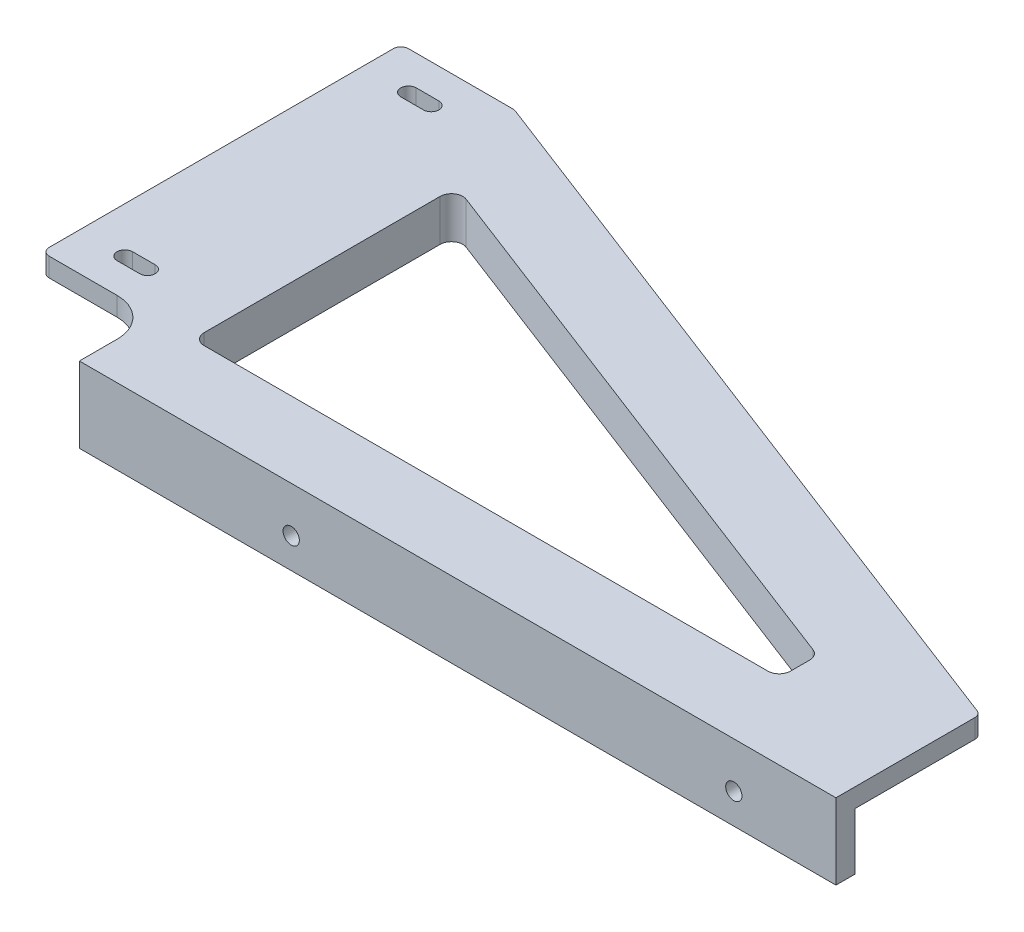
SolidWorks part; units mm, degrees
ref_plane "Front" through (0, 0, 0) normal (0, 0, 1) x (1, 0, 0)
ref_plane "Top" through (0, 0, 0) normal (0, 1, 0) x (1, 0, 0)
ref_plane "Right" through (0, 0, 0) normal (1, 0, 0) x (0, 0, -1)
other "Configuration Table"
sketch "Sketch1" plane through (0, 0, 0) normal (0, 1, 0) x (1, 0, 0)
  line L0 (-100, 0) -> (100, 0)
  line L1 (100, 0) -> (100, 38.1)
  line L3 (-130, 115) -> (-130, 20)
  line L4 (-100, 0) -> (-100, 10)
  line L5 (-110, 20) -> (-130, 20)
  line L6 (-130, 115) -> (-100, 115)
  line L7 (100, 38.1) -> (-100, 115)
  arc A0 (-100, 10) -> (-110, 20) centre (-110, 10) ccw
  point P0 (0, 0)
  dimension "D6" = 10
  dimension "D1" = 115
  dimension "D2" = 230
  dimension "D3" = 38.1
  dimension "D4" = 30
  dimension "D5" = 20
extrude "Boss-Extrude1" add sketch "Sketch1" along normal blind 5 contours L3 L5 A0 L4 L0 L1 L7 L6
sketch "Sketch2" plane through (0, 0, 0) normal (0, -1, 0) x (1, 0, 0)
  line L0 (-100, -5) -> (100, -5)
  line L2 (100, 0) -> (100, -38.1) construction
  line L3 (100, -5) -> (100, 0)
  line L4 (100, 0) -> (-100, 0)
  line L5 (-100, 0) -> (-100, -5)
  line L8 (-100, 0) -> (-100, -10) construction
  dimension "D1" = 5
extrude "Boss-Extrude2" add sketch "Sketch2" along normal blind 15 contours L4 L5 L0 L3
sketch "Sketch5" plane through (0, 0, 0) normal (0, -1, 0) x (1, 0, 0)
  line L1 (-53.5, -5) -> (-34.5, -5)
  line L3 (-48.5, -10) -> (-39.5, -10)
  line L5 (-53.5, -5) -> (-39.5, -10) construction
  line L6 (-34.5, -5) -> (-48.5, -10) construction
  line L7 (-100, -5) -> (100, -5) construction
  line L10 (68.5, -10) -> (77.5, -10)
  line L12 (73, 36.5599) -> (73, -36.1824) construction
  line L13 (77.5, -10) -> (82.5, -5)
  line L15 (-39.5, -10) -> (-34.5, -5)
  line L17 (-44, -13.3089) -> (-44, -5.4456) construction
  line L18 (-48.5, -10) -> (-53.5, -5)
  line L20 (-100, -5) -> (100, -5) construction
  line L21 (68.5, -10) -> (63.5, -5)
  line L22 (63.5, -5) -> (82.5, -5)
  line L23 (-100, 0) -> (-100, -5) construction
  point P4 (-44, -8.3929)
  point P5 (73, -10)
  point P11 (73, -10.0372)
  dimension "D1" = 9
  dimension "D2" = 5
  dimension "D3" = 9
  dimension "D4" = 5
  dimension "D5" = 56
  dimension "D6" = 173
  dimension "D7" = 225
  dimension "D8" = 135
extrude "Boss-Extrude3" add sketch "Sketch5" along normal up to surface (15 mm away) up to face at (0, -15, -2.5)
sketch "Sketch6" plane through (0, 0, 0) normal (0, 0, 1) x (1, 0, 0)
  line L2 (-100, 5) -> (100, 5) construction
  line L3 (-100, -15) -> (-100, 0) construction
  circle A0 centre (-44, -7) radius 2.15
  circle A1 centre (73, -7) radius 2.15
  point P8 (0, 0)
  dimension "D1" = 4.3
  dimension "D2" = 4.3
  dimension "D3" = 56
  dimension "D4" = 173
  dimension "D5" = 12
extrude "Cut-Extrude2" cut sketch "Sketch6" against normal through all
sketch "Sketch7" plane through (0, 0, -10) normal (0, 0, -1) x (-1, 0, 0)
  line L1 (-73, -11.0992) -> (-69.45, -9.0496)
  line L2 (-69.45, -9.0496) -> (-69.45, -4.9504)
  line L3 (-69.45, -4.9504) -> (-73, -2.9008)
  line L4 (-73, -2.9008) -> (-76.55, -4.9504)
  line L5 (-76.55, -4.9504) -> (-76.55, -9.0496)
  line L6 (-76.55, -9.0496) -> (-73, -11.0992)
  line L7 (47.55, -9.0496) -> (47.55, -4.9504)
  line L8 (47.55, -4.9504) -> (44, -2.9008)
  line L9 (44, -2.9008) -> (40.45, -4.9504)
  line L10 (40.45, -4.9504) -> (40.45, -9.0496)
  line L11 (40.45, -9.0496) -> (44, -11.0992)
  line L12 (44, -11.0992) -> (47.55, -9.0496)
  circle A0 centre (-73, -7) radius 3.55 construction
  circle A1 centre (44, -7) radius 3.55 construction
  point P1 (59, -7)
  dimension "D1" = 7.1
  dimension "D2" = 7.1
extrude "Cut-Extrude3" cut sketch "Sketch7" against normal blind 3.2
sketch "Sketch9" plane through (0, 0, 0) normal (0, -1, 0) x (1, 0, 0)
  line L0 (-130, -115) -> (-130, -20) construction
  line L1 (-125, -35.5) -> (-105, -35.5)
  line L2 (-125, -35.5) -> (-125, -24.5)
  line L3 (-125, -24.5) -> (-105, -24.5)
  line L4 (-105, -35.5) -> (-105, -24.5)
  line L5 (-125, -35.5) -> (-105, -24.5) construction
  line L6 (-125, -24.5) -> (-105, -35.5) construction
  line L7 (-125, -110.5) -> (-105, -110.5)
  line L8 (-125, -110.5) -> (-125, -99.5)
  line L9 (-125, -99.5) -> (-105, -99.5)
  line L10 (-105, -110.5) -> (-105, -99.5)
  line L11 (-125, -110.5) -> (-105, -99.5) construction
  line L12 (-125, -99.5) -> (-105, -110.5) construction
  line L13 (-130, -67.5) -> (-65.95, -67.5) construction
  point P0 (-115, -30)
  point P5 (-115, -105)
  point P10 (0, 0)
  point P15 (0, 0)
  point P16 (0, 0)
  point P17 (0, 0)
  dimension "D1" = 20
  dimension "D2" = 11
  dimension "D3" = 75
  dimension "D4" = 15
extrude "Boss-Extrude4" add sketch "Sketch9" along normal blind 2
chamfer "Chamfer1" distance 2 angle 45 8 edges at (-105, 0, -30) (-115, 0, -35.5) (-115, 0, -24.5) (-125, 0, -30) (-115, 0, -99.5) (-125, 0, -105) (-105, 0, -105) (-115, 0, -110.5)
sketch "Sketch8" plane through (0, -2, 0) normal (0, -1, 0) x (1, 0, 0)
  line L0 (-115, 7.2671) -> (-115, -126.9464) construction
  line L1 (-130, -115) -> (-130, -20) construction
  line L2 (-118, -30) -> (-112, -30) construction
  line L3 (-118, -27.95) -> (-112, -27.95)
  line L4 (-118, -32.05) -> (-112, -32.05)
  line L5 (-118, -105) -> (-112, -105) construction
  line L6 (-118, -102.95) -> (-112, -102.95)
  line L7 (-118, -107.05) -> (-112, -107.05)
  line L8 (-130, -67.5) -> (-41.0791, -67.5) construction
  arc A0 (-118, -27.95) -> (-118, -32.05) centre (-118, -30) ccw
  arc A1 (-112, -32.05) -> (-112, -27.95) centre (-112, -30) ccw
  arc A2 (-118, -102.95) -> (-118, -107.05) centre (-118, -105) ccw
  arc A3 (-112, -107.05) -> (-112, -102.95) centre (-112, -105) ccw
  point P6 (-115, -30)
  point P11 (-115, -105)
  point P18 (0, 0)
  dimension "D1" = 15
  dimension "D2" = 4.1
  dimension "D3" = 6
  dimension "D4" = 4.1
  dimension "D5" = 6
  dimension "D6" = 75
extrude "Cut-Extrude4" cut sketch "Sketch8" against normal through all
sketch "Sketch10" plane through (0, 0, 0) normal (0, -1, 0) x (1, 0, 0)
  line L0 (-90, -31.3983) -> (-90, -85.3599)
  line L1 (-85.9233, -88.1601) -> (63.0767, -30.8696)
  line L2 (65, -28.0694) -> (65, -23)
  line L3 (62, -20) -> (-87, -20)
  line L4 (-90, -23) -> (-90, -31.3983)
  line L5 (-130, -115) -> (-130, -20) construction
  line L7 (100, -38.1) -> (-100, -115) construction
  line L8 (-34.5, -5) -> (63.5, -5) construction
  line L9 (100, -5) -> (100, -38.1) construction
  arc A0 (-90, -85.3599) -> (-85.9233, -88.1601) centre (-87, -85.3599) ccw
  arc A1 (63.0767, -30.8696) -> (65, -28.0694) centre (62, -28.0694) ccw
  arc A2 (65, -23) -> (62, -20) centre (62, -23) ccw
  arc A3 (-87, -20) -> (-90, -23) centre (-87, -23) ccw
  dimension "D5" = 3
  dimension "D1" = 40
  dimension "D2" = 20
  dimension "D3" = 15
  dimension "D4" = 35
extrude "Cut-Extrude5" cut sketch "Sketch10" against normal through all contours L3 A3 L4 L0 A0 L1 A1 L2 A2
sketch "Sketch11" plane through (0, 0, 0) normal (0, -1, 0) x (1, 0, 0)
  line L6 (-90, -23) -> (-90, -85.3599) construction
  line L7 (-85.9233, -88.1601) -> (63.0767, -30.8696) construction
  line L8 (65, -28.0694) -> (65, -23) construction
  line L13 (62, -20) -> (-87, -20) construction
  line L14 (-90, -23) -> (-90, -85.3599)
  line L15 (-85.9233, -88.1601) -> (63.0767, -30.8696)
  line L16 (65, -28.0694) -> (65, -23)
  line L17 (62, -20) -> (-87, -20)
  line L18 (62, -17.75) -> (-87, -17.75)
  line L19 (-92.25, -23) -> (-92.25, -85.3599)
  line L20 (-85.1159, -90.2602) -> (63.8841, -32.9697)
  line L21 (67.25, -28.0694) -> (67.25, -23)
  arc A0 (-87, -20) -> (-90, -23) centre (-87, -23) ccw construction
  arc A1 (-90, -85.3599) -> (-85.9233, -88.1601) centre (-87, -85.3599) ccw construction
  arc A2 (63.0767, -30.8696) -> (65, -28.0694) centre (62, -28.0694) ccw construction
  arc A3 (65, -23) -> (62, -20) centre (62, -23) ccw construction
  arc A12 (-87, -20) -> (-90, -23) centre (-87, -23) ccw
  arc A13 (-90, -85.3599) -> (-85.9233, -88.1601) centre (-87, -85.3599) ccw
  arc A14 (63.0767, -30.8696) -> (65, -28.0694) centre (62, -28.0694) ccw
  arc A15 (65, -23) -> (62, -20) centre (62, -23) ccw
  arc A16 (-87, -17.75) -> (-92.25, -23) centre (-87, -23) ccw
  arc A17 (-92.25, -85.3599) -> (-85.1159, -90.2602) centre (-87, -85.3599) ccw
  arc A18 (63.8841, -32.9697) -> (67.25, -28.0694) centre (62, -28.0694) ccw
  arc A19 (67.25, -23) -> (62, -17.75) centre (62, -23) ccw
  dimension "D1" = 2.25
extrude "Boss-Extrude5" add sketch "Sketch11" along normal blind 6
fillet "Fillet1" radius 2 4 edges at (-130, 2.5, -20) (-130, 2.5, -115) (-100, 2.5, -115) (100, 2.5, -38.1)
